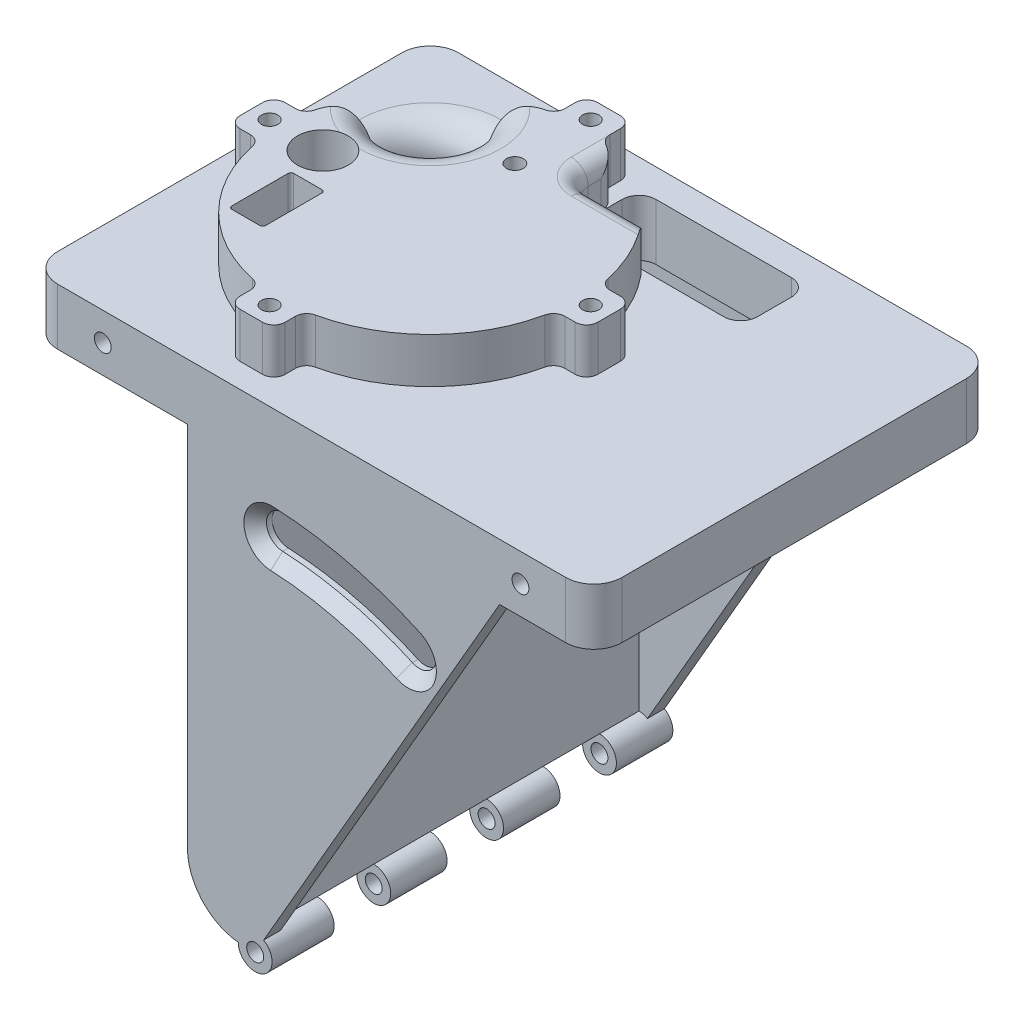
SolidWorks part; units mm, degrees
material "ABS"
ref_plane "Front Plane" through (0, 0, 0) normal (0, 0, 1) x (1, 0, 0)
ref_plane "Top Plane" through (0, 0, 0) normal (0, 1, 0) x (1, 0, 0)
ref_plane "Right Plane" through (0, 0, 0) normal (1, 0, 0) x (0, 0, -1)
sketch "Sketch1" plane through (0, 0, 0) normal (0, 1, 0) x (1, 0, 0)
  circle A0 centre (0, 0) radius 26.5
  dimension "D1" = 53
extrude "Boss-Extrude1" add sketch "Sketch1" along normal blind 8
sketch "Sketch2" plane through (0, 0, 0) normal (0, -1, 0) x (1, 0, 0)
  line L0 (0, 0) -> (0, 31.7947) construction
  line L1 (-4, 31.6964) -> (4, 31.6964)
  line L2 (-4, 31.6964) -> (-4, 26.1964)
  line L3 (4, 31.6964) -> (4, 26.1964)
  line L4 (4, 26.1964) -> (-4, 26.1964)
  line L5 (-4, 28.4464) -> (4, 28.4464) construction
  circle A0 centre (0, 0) radius 26.5 construction
  circle A1 centre (0, 28.4464) radius 1.45
  dimension "D4" = 2.9
  dimension "D1" = 8
  dimension "D2" = 5.5
  dimension "D3" = 3.25
extrude "Boss-Extrude2" add sketch "Sketch2" against normal blind 8
fillet "Fillet1" radius 2 4 edges at (4, 4, 26.1964) (4, 4, 31.6964) (-4, 4, 26.1964) (-4, 4, 31.6964)
pattern_circular "CirPattern1" count 4 over 360 about axis through (0, 0, 0) along (0, 1, 0) of "Boss-Extrude2", "Fillet1"
sketch "Sketch4" plane through (0, 0, 0) normal (0, 1, 0) x (1, 0, 0)
  line L0 (18, 32) -> (18, 16) construction
  line L1 (-30, 35) -> (60, 35)
  line L2 (18, 16) -> (-16, 16) construction
  line L6 (-32, 0) -> (0, 0)
  line L7 (-32, 0) -> (-32, 32)
  line L8 (-32, 32) -> (0, 32)
  line L9 (0, 0) -> (0, 32)
  line L10 (-32, 0) -> (0, 32) construction
  line L11 (-32, 32) -> (0, 0) construction
  line L12 (-35, 30) -> (-35, -31)
  line L13 (-30, -36) -> (60, -36)
  line L14 (8, -33) -> (28, -33)
  line L15 (8, -33) -> (8, 32)
  line L16 (8, 32) -> (28, 32)
  line L17 (28, -33) -> (28, 32)
  line L18 (8, -33) -> (28, 32) construction
  line L19 (8, 32) -> (28, -33) construction
  line L20 (65, 30) -> (65, -31)
  arc A0 (65, -31) -> (60, -36) centre (60, -31) cw
  arc A1 (-30, -36) -> (-35, -31) centre (-30, -31) cw
  arc A2 (-35, 30) -> (-30, 35) centre (-30, 30) cw
  arc A3 (65, 30) -> (60, 35) centre (60, 30) ccw
  point P9 (-35, -36)
  point P23 (-35, 35)
  dimension "D11" = 5
  dimension "D1" = 71
  dimension "D2" = 20
  dimension "D3" = 32
  dimension "D4" = 32
  dimension "D6" = 65
  dimension "D7" = 16
  dimension "D8" = 34
  dimension "D9" = 100
  dimension "D10" = 3
  dimension "D12" = 3
extrude "Boss-Extrude4" add sketch "Sketch4" against normal blind 10 contours A3 L20 A0 L13 A1 L12 A2 L1
sketch "Sketch7" plane through (0, 8, 0) normal (0, 1, 0) x (1, 0, 0)
  line L0 (0, 0) -> (0, 15) construction
  circle A0 centre (0, 15) radius 1.5
  dimension "D1" = 3
  dimension "D2" = 15
extrude "Cut-Extrude2" cut sketch "Sketch7" against normal blind 3
sketch "Sketch8" plane through (0, -10, 0) normal (0, -1, 0) x (1, 0, 0)
  line L0 (-16, 0) -> (0, 0) construction
  line L1 (-16, 0) -> (-16, -16) construction
  line L5 (5, 36) -> (5, -35)
  line L6 (5, -35) -> (2, -35)
  line L9 (-30, -35) -> (60, -35) construction
  line L10 (2, 32) -> (-7, 32)
  line L11 (-7, 32) -> (-7, 36)
  line L12 (-30, 36) -> (60, 36) construction
  line L15 (-7, 2) -> (-7, 6)
  line L16 (-7, 6) -> (2, 6)
  line L17 (2, 6) -> (2, 32)
  line L18 (-7, 36) -> (5, 36)
  line L19 (-16, -26) -> (-16, -35) construction
  line L21 (2, 2) -> (2, -6)
  line L22 (2, -35) -> (2, -26)
  line L23 (-16, -6) -> (2, -6)
  line L24 (-16, -26) -> (2, -26)
  line L25 (-7, 2) -> (2, 2)
  arc A0 (-16, -6) -> (-16, -26) centre (-16, -16) ccw
  point P6 (2, -30.5)
  point P13 (3.5, -35)
  dimension "D3" = 20
  dimension "D1" = 16
  dimension "D2" = 16
  dimension "D4" = 3
  dimension "D5" = 4
  dimension "D6" = 18
  dimension "D7" = 12
  dimension "D8" = 12
  dimension "D9" = 18
  dimension "D10" = 2
  dimension "D11" = 4
extrude "Boss-Extrude7" add sketch "Sketch8" along normal blind 20
sketch "Sketch3" plane through (0, 8, 0) normal (0, 1, 0) x (1, 0, 0)
  line L0 (0, 0) -> (-28.4464, 0) construction
  line L1 (-19, 0) -> (-15.5663, -6.1) construction
  line L2 (-15.5663, -6.1) -> (-15.5663, 0) construction
  line L4 (-18.0663, -6.1) -> (-13.0663, -6.1)
  line L5 (-18.5663, -6.6) -> (-18.5663, -16.6)
  line L6 (-18.0663, -17.1) -> (-13.0663, -17.1)
  line L7 (-12.5663, -6.6) -> (-12.5663, -16.6)
  circle A0 centre (-19, 0) radius 4.5
  arc A1 (-18.5663, -16.6) -> (-18.0663, -17.1) centre (-18.0663, -16.6) ccw
  arc A2 (-13.0663, -17.1) -> (-12.5663, -16.6) centre (-13.0663, -16.6) ccw
  arc A3 (-12.5663, -6.6) -> (-13.0663, -6.1) centre (-13.0663, -6.6) ccw
  arc A4 (-18.0663, -6.1) -> (-18.5663, -6.6) centre (-18.0663, -6.6) ccw
  point P12 (-15.5663, -6.1)
  point P15 (-18.5663, -17.1)
  point P20 (-12.5663, -6.1)
  point P23 (-18.5663, -6.1)
  dimension "D6" = 9
  dimension "D7" = 0.5
  dimension "D1" = 19
  dimension "D2" = 7
  dimension "D3" = 6.1
  dimension "D4" = 6
  dimension "D5" = 11
extrude "Cut-Extrude4" cut sketch "Sketch3" against normal up to next
sketch "Sketch13" plane through (0, -30, 0) normal (0, -1, 0) x (1, 0, 0)
  line L1 (-32, 0) -> (0, 0)
  line L2 (-32, 0) -> (-32, -32)
  line L3 (-32, -32) -> (0, -32)
  line L4 (0, 0) -> (0, -32)
  line L5 (-32, 0) -> (0, -32) construction
  line L6 (-32, -32) -> (0, 0) construction
  point P0 (-16, -16)
  dimension "D1" = 32
  dimension "D2" = 32
extrude "Boss-Extrude15" add sketch "Sketch13" along normal blind 10
sketch "Sketch15" plane through (0, -30, 0) normal (0, -1, 0) x (1, 0, 0)
  line L0 (-7, 36) -> (-7, 32)
  line L1 (-7, 32) -> (2, 32)
  line L2 (2, 32) -> (2, 6)
  line L3 (2, 6) -> (-7, 6)
  line L4 (-7, 6) -> (-7, 2)
  line L5 (-7, 2) -> (2, 2)
  line L6 (2, 2) -> (2, -35)
  line L7 (2, -35) -> (5, -35)
  line L8 (5, -35) -> (5, 36)
  line L9 (5, 36) -> (-7, 36)
extrude "Boss-Extrude16" add sketch "Sketch15" along normal blind 55
sketch "Sketch16" plane through (0, 0, -35) normal (0, 0, -1) x (-1, 0, 0)
  circle A1 centre (-5, -85) radius 3
extrude "Boss-Extrude17" add sketch "Sketch16" against normal blind 71
ref_plane "Plane1" through (0, 0, -25) normal (0, 0, -1) x (-1, 0, 0)
ref_plane "Plane3" through (0, 0, -5) normal (0, 0, -1) x (-1, 0, 0)
sketch "Sketch18" plane through (0, 0, -25) normal (0, 0, -1) x (-1, 0, 0)
  circle A0 centre (-5, -85) radius 3
extrude "Cut-Extrude5" cut sketch "Sketch18" against normal blind 10
sketch "Sketch19" plane through (0, 0, -5) normal (0, 0, -1) x (-1, 0, 0)
  circle A0 centre (-5, -85) radius 3
extrude "Cut-Extrude6" cut sketch "Sketch19" against normal blind 10
sketch "Sketch21" plane through (0, 0, -35) normal (0, 0, -1) x (-1, 0, 0)
  line L0 (-5, -10) -> (-5, -85)
  line L1 (-5, -85) -> (-48.3013, -10)
  line L2 (-5, -10) -> (-60, -10) construction
  line L3 (-48.3013, -10) -> (-5, -10)
  dimension "D1" = 30
extrude "Boss-Extrude18" add sketch "Sketch21" against normal blind 3
sketch "Sketch22" plane through (0, 0, 36) normal (0, 0, 1) x (1, 0, 0)
  line L0 (5, -85) -> (5, -10)
  line L1 (5, -10) -> (48.3013, -10)
  line L2 (48.3013, -10) -> (5, -85)
extrude "Boss-Extrude19" add sketch "Sketch22" against normal blind 3
ref_plane "Plane5" through (0, 0, 15) normal (0, 0, -1) x (-1, 0, 0)
sketch "Sketch24" plane through (0, 0, 15) normal (0, 0, -1) x (-1, 0, 0)
  circle A0 centre (-5, -85) radius 3
extrude "Cut-Extrude7" cut sketch "Sketch24" against normal blind 10
fillet "Fillet6" radius 10 2 edges at (-7, -85, 34) (-7, -85, 4)
sketch "Sketch29" plane through (0, 0, -35) normal (0, 0, -1) x (-1, 0, 0)
  line L0 (-5, -85) -> (-5, -20) construction
  line L1 (-5, -85) -> (-33.356, -23.1944) construction
  line L2 (-8, -20.0693) -> (-5, -85) construction
  line L3 (-5, -85) -> (-34.8318, -27.1721) construction
  arc A0 (-8.1385, -17.0725) -> (-33.356, -23.1944) centre (-5, -85) ccw
  arc A1 (-7.8615, -23.0661) -> (-30.854, -28.6478) centre (-5, -85) ccw
  arc A2 (-33.356, -23.1944) -> (-30.854, -28.6478) centre (-32.105, -25.9211) ccw
  arc A3 (-32.105, -25.9211) -> (-5, -20) centre (-5, -85) cw construction
  arc A4 (-7.8615, -23.0661) -> (-8.1385, -17.0725) centre (-8, -20.0693) ccw
  dimension "D1" = 6
  dimension "D3" = 65
  dimension "D2" = 22
extrude "Cut-Extrude10" cut sketch "Sketch29" against normal through all
sketch "Sketch31" plane through (0, 0, -35) normal (0, 0, -1) x (-1, 0, 0)
  circle A0 centre (-5, -85) radius 1.5
  dimension "D1" = 3
extrude "Cut-Extrude11" cut sketch "Sketch31" against normal through all
sketch "Sketch32" plane through (0, -40, 0) normal (0, -1, 0) x (1, 0, 0)
  line L2 (-32, -32) -> (0, 0) construction
  circle A4 centre (-16, -16) radius 7.5
  point P1 (-16, -16)
  dimension "D1" = 15
extrude "Cut-Extrude12" cut sketch "Sketch32" against normal through all
sketch "Sketch33" plane through (0, -40, 0) normal (0, -1, 0) x (1, 0, 0)
  line L0 (-2.5044, -29.4956) -> (-29.4956, -29.4956) construction
  line L2 (0, 0) -> (-32, 0)
  line L3 (0, 0) -> (0, -32)
  line L4 (0, -32) -> (-32, -32)
  line L5 (-32, 0) -> (-32, -32)
  line L6 (0, 0) -> (-32, -32) construction
  line L7 (0, -32) -> (-32, 0) construction
  line L8 (-29.4956, -29.4956) -> (-29.4956, -2.5044) construction
  line L9 (-29.4956, -2.5044) -> (-2.5044, -2.5044) construction
  line L10 (-2.5044, -2.5044) -> (-2.5044, -29.4956) construction
  circle A0 centre (-29.4956, -2.5044) radius 1
  circle A1 centre (-2.5044, -2.5044) radius 1
  circle A2 centre (-29.4956, -29.4956) radius 1
  circle A3 centre (-2.5044, -29.4956) radius 1
  point P0 (-16, -16)
  dimension "D2" = 2
  dimension "D1" = 2.5044
extrude "Cut-Extrude13" cut sketch "Sketch33" against normal blind 5 contours A0 | A1 | A3 | A2
fillet "Fillet7" radius 5 1 edges at (-16, -40, -23.5)
fillet "Fillet8" radius 10 3 edges at (-8, -30, -6) (-8, -30, -26) (-26, -30, -16)
fillet "Fillet9" radius 5 4 edges at (-10.6967, 8, -10.6967) (-22.9662, 4, -13.2213) (-13.2213, 4, -22.9662) (-21.3033, 0, -21.3033)
chamfer "Chamfer1" distance 2 angle 45 8 edges at (34.8318, -27.1721, 36) (21.042, -18.9193, 36) (5.0032, -19.9308, 36) (19.6265, -24.75, 36) (34.8318, -27.1721, -35) (21.042, -18.9193, -35) (5.0032, -19.9308, -35) (19.6265, -24.75, -35)
fillet "Fillet10" radius 3 4 edges at (0, -35, 0) (-32, -35, 0) (-32, -35, -32) (0, -35, -32)
sketch "Sketch37" plane through (0, -10, 0) normal (0, -1, 0) x (1, 0, 0)
  line L1 (5, -32) -> (5, 33) construction
  line L2 (10, -18) -> (34, -18)
  line L3 (7, -21) -> (7, -27)
  line L4 (10, -30) -> (34, -30)
  line L5 (37, -21) -> (37, -27)
  line L6 (5, -32) -> (48.3013, -32) construction
  arc A0 (34, -18) -> (37, -21) centre (34, -21) cw
  arc A1 (34, -30) -> (37, -27) centre (34, -27) ccw
  arc A2 (7, -27) -> (10, -30) centre (10, -27) ccw
  arc A3 (7, -21) -> (10, -18) centre (10, -21) cw
  point P14 (7, -30)
  point P17 (7, -18)
  dimension "D5" = 3
  dimension "D1" = 30
  dimension "D2" = 12
  dimension "D3" = 2
  dimension "D4" = 2
extrude "Cut-Extrude14" cut sketch "Sketch37" against normal through all
fillet "Fillet12" radius 3 5 edges at (7, 4, -25.5588) (7, 8, -23.2794) (7.8787, 8, -18.8787) (14.7243, 8, -18) (19.4487, 4, -18)
sketch "Sketch38" plane through (0, 0, -35) normal (0, 0, -1) x (-1, 0, 0)
  circle A0 centre (-52, -5) radius 1.5
  circle A1 centre (22, -5) radius 1.5
  dimension "D1" = 3
  dimension "D2" = 3
extrude "Cut-Extrude15" cut sketch "Sketch38" against normal blind 3
sketch "Sketch39" plane through (0, 0, 36) normal (0, 0, 1) x (1, 0, 0)
  circle A0 centre (-22, -5) radius 1.5
  circle A1 centre (52, -5) radius 1.5
  dimension "D1" = 3
  dimension "D2" = 3
extrude "Cut-Extrude16" cut sketch "Sketch39" against normal blind 3
